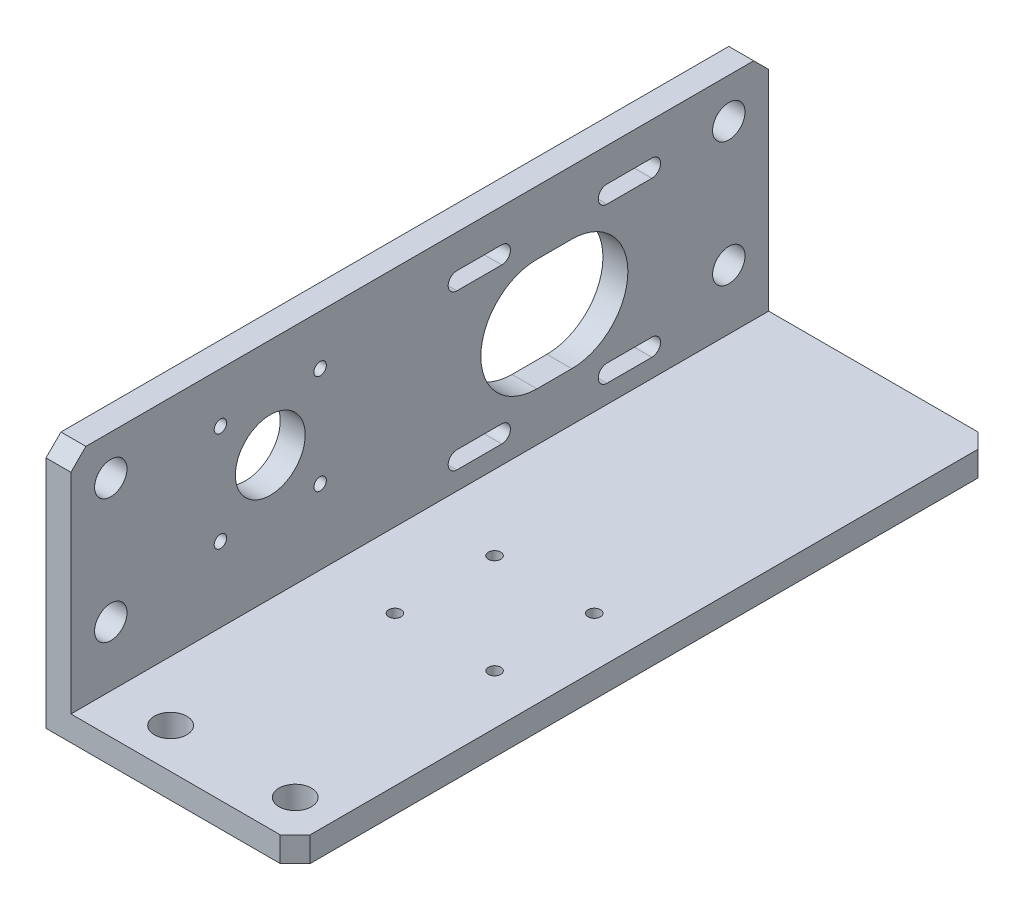
SolidWorks part; units mm, degrees
material "Lega 1060"
ref_plane "Piano frontale" through (0, 0, 0) normal (0, 0, 1) x (1, 0, 0)
ref_plane "Piano superiore" through (0, 0, 0) normal (0, 1, 0) x (1, 0, 0)
ref_plane "Piano destro" through (0, 0, 0) normal (1, 0, 0) x (0, 0, -1)
sketch "Schizzo1" plane through (0, 0, 0) normal (0, 0, 1) x (1, 0, 0)
  line L0 (0, 0) -> (0, 50)
  line L1 (0, 50) -> (5, 50)
  line L2 (5, 50) -> (5, 5)
  line L3 (5, 5) -> (50, 5)
  line L4 (50, 5) -> (50, 0)
  line L5 (50, 0) -> (0, 0)
  dimension "D1" = 5
  dimension "D2" = 5
  dimension "D3" = 50
  dimension "D4" = 50
extrude "Estrusione-Estrusione1" add sketch "Schizzo1" along normal blind 140
sketch "Schizzo2" plane through (0, 0, 0) normal (0, -1, 0) x (1, 0, 0)
  line L0 (5.4524, 132) -> (42.7933, 132) construction
  line L1 (0, 140) -> (50, 140) construction
  line L5 (50, 140) -> (50, 0) construction
  point P4 (17, 132)
  point P5 (42, 132)
  dimension "D1" = 8
  dimension "D2" = 25
  dimension "D3" = 8
sketch "Schizzo3" plane through (0, 0, 0) normal (-1, 0, 0) x (0, 0, 1)
  line L0 (132, 44.621) -> (132, 5.772) construction
  line L1 (140, 50) -> (140, 0) construction
  line L2 (140, 50) -> (0, 50) construction
  point P4 (132, 42)
  point P5 (132, 17)
  dimension "D1" = 8
  dimension "D2" = 8
  dimension "D3" = 25
hole_wizard "Foro Ø6.5 (6.5)-1" positions "Schizzo5" profile "Schizzo4" hole size "Ø6.5" standard "ISO" end condition through all
sketch "Schizzo5" plane through (0, 0, 0) normal (0, -1, 0) x (-1, 0, 0)
  point P0 (-17, -132)
  point P3 (-42, -132)
sketch "Schizzo4" plane through (17, 0, 132) normal (1, 0, 0) x (0, 0, -1)
  line L0 (0, 0) -> (0, 50)
  line L1 (0, 50) -> (3.25, 50)
  line L2 (3.25, 50) -> (3.25, 0)
  line L5 (3.25, 0) -> (0, 0)
  line L11 (0, -6.35) -> (0, 107.95) construction
  dimension "Thru Hole Dia." = 6.5
  dimension "Thru Hole Depth" = 50
hole_wizard "Foro Ø6.5 (6.5)-2" positions "Schizzo7" profile "Schizzo6" hole size "Ø6.5" standard "ISO"
sketch "Schizzo7" plane through (0, 0, 0) normal (-1, 0, 0) x (0, 0, 1)
  point P1 (132, 42)
  point P4 (132, 17)
sketch "Schizzo6" plane through (0, 42, 132) normal (0, 1, 0) x (0, 0, 1)
  line L0 (0, 0) -> (0, 6.9528)
  line L1 (0, 6.9528) -> (3.25, 5)
  line L2 (3.25, 5) -> (3.25, 0)
  line L5 (3.25, 0) -> (0, 0)
  line L10 (0, 6.9528) -> (-3.25, 5) construction
  line L11 (0, -6.35) -> (0, 107.95) construction
  dimension "Hole Dia." = 6.5
  dimension "Hole Depth" = 5
  dimension "Drill Angle" = 118
ref_plane "Piano1" through (0, 0, 70) normal (0, 0, 1) x (1, 0, 0)
mirror "Specchia1" about plane through (0, 0, 70) normal (0, 0, 1) of "Foro Ø6.5 (6.5)-2"
sketch "Schizzo8" plane through (0, 0, 0) normal (0, -1, 0) x (1, 0, 0)
  line L0 (30, 80) -> (7.0316, 80) construction
  line L1 (30, 80) -> (-7.1051, 42.8949) construction
  line L2 (0, 140) -> (50, 140) construction
  line L3 (50, 140) -> (50, 0) construction
  circle A0 centre (20, 70) radius 1.75
  circle A1 centre (20, 90) radius 1.75
  circle A2 centre (40, 90) radius 1.75
  circle A3 centre (40, 70) radius 1.75
  point P18 (30, 80)
  dimension "D3" = 3.5
  dimension "D1" = 60
  dimension "D2" = 20
  dimension "D4" = 45
  dimension "D5" = 20
  dimension "D6" = 4
sketch "Schizzo9" plane through (0, 0, 0) normal (-1, 0, 0) x (0, 0, 1)
  line L2 (140, 50) -> (0, 50) construction
  line L3 (140, 50) -> (140, 0) construction
  circle A4 centre (100, 30) radius 7
  point P18 (100, 30)
  dimension "D7" = 14
  dimension "D1" = 20
  dimension "D2" = 40
extrude "Taglio-Estrusione2" cut sketch "Schizzo9" against normal up to next
sketch "Schizzo11" plane through (0, 0, 0) normal (-1, 0, 0) x (0, 0, 1)
  line L0 (32.6037, 26) -> (56.4009, 26) construction
  line L1 (62.5563, 10.4437) -> (53.5563, 10.4437) construction
  line L2 (140, 0) -> (0, 0) construction
  line L3 (62.5563, 41.5563) -> (53.5563, 41.5563) construction
  line L4 (62.5563, 39.8063) -> (53.5563, 39.8063)
  line L5 (62.5563, 43.3063) -> (53.5563, 43.3063)
  line L6 (43, 26) -> (43, 48.418) construction
  line L7 (62.5563, 12.1937) -> (53.5563, 12.1937)
  line L8 (62.5563, 8.6937) -> (53.5563, 8.6937)
  line L9 (23.4437, 10.4437) -> (32.4437, 10.4437) construction
  line L10 (23.4437, 12.1937) -> (32.4437, 12.1937)
  line L11 (23.4437, 8.6937) -> (32.4437, 8.6937)
  line L12 (23.4437, 41.5563) -> (32.4437, 41.5563) construction
  line L13 (23.4437, 39.8063) -> (32.4437, 39.8063)
  line L14 (23.4437, 43.3063) -> (32.4437, 43.3063)
  line L15 (46.5, 26) -> (39.5, 26) construction
  line L16 (46.5, 14.75) -> (39.5, 14.75)
  line L17 (46.5, 37.25) -> (39.5, 37.25)
  arc A1 (62.5563, 39.8063) -> (62.5563, 43.3063) centre (62.5563, 41.5563) ccw
  arc A2 (62.5563, 12.1937) -> (62.5563, 8.6937) centre (62.5563, 10.4437) cw
  arc A3 (53.5563, 8.6937) -> (53.5563, 12.1937) centre (53.5563, 10.4437) cw
  arc A4 (23.4437, 12.1937) -> (23.4437, 8.6937) centre (23.4437, 10.4437) ccw
  arc A5 (32.4437, 8.6937) -> (32.4437, 12.1937) centre (32.4437, 10.4437) ccw
  arc A7 (53.5563, 43.3063) -> (53.5563, 39.8063) centre (53.5563, 41.5563) ccw
  arc A8 (23.4437, 39.8063) -> (23.4437, 43.3063) centre (23.4437, 41.5563) cw
  arc A9 (32.4437, 43.3063) -> (32.4437, 39.8063) centre (32.4437, 41.5563) cw
  arc A10 (46.5, 14.75) -> (46.5, 37.25) centre (46.5, 26) ccw
  arc A11 (39.5, 37.25) -> (39.5, 14.75) centre (39.5, 26) ccw
  point P10 (58.0563, 10.4437)
  point P13 (58.0563, 41.5563)
  point P18 (27.9437, 10.4437)
  point P20 (43, 26)
  point P33 (27.9437, 41.5563)
  point P40 (43, 26)
  dimension "D5" = 7
  dimension "D1" = 22.5
  dimension "D4" = 26
  dimension "D8" = 3.5
  dimension "D9" = 9
extrude "Taglio-Estrusione4" cut sketch "Schizzo11" against normal up to next
chamfer "Smusso1" distance 3 angle 45 4 edges at (50, 2.5, 0) (2.5, 50, 0) (2.5, 50, 140) (50, 2.5, 140)
sketch "Sketch4" plane through (0, 0, 0) normal (-1, 0, 0) x (0, 0, 1)
  line L0 (100, 30) -> (100, 45.3374) construction
  line L1 (100, 30) -> (85.4455, 44.5545) construction
  line L2 (100, 30) -> (85.4455, 30) construction
  point P3 (90, 40)
  point P5 (110, 40)
  point P6 (90, 20)
  point P8 (110, 20)
  dimension "D1" = 45
  dimension "D2" = 10
hole_wizard "M3 Tapped Hole1" positions "3DSketch3" profile "Sketch5" tap size "M3" standard "ISO" end condition through all
sketch3d "3DSketch3"
  point P0 (0, 40, 90)
  point P3 (0, 40, 110)
  point P6 (0, 20, 110)
  point P9 (0, 20, 90)
sketch "Sketch5" plane through (0, 40, 90) normal (0, 1, 0) x (0, 0, 1)
  line L0 (0, 0) -> (0, 50)
  line L1 (0, 50) -> (1.25, 50)
  line L2 (1.25, 50) -> (1.25, 0)
  line L5 (1.25, 0) -> (0, 0)
  line L11 (0, -6.35) -> (0, 107.95) construction
  dimension "Thru Tap Drill Dia." = 2.5
  dimension "Thru Tap Drill Depth" = 50
cosmetic thread "Cosmetic Thread1" parameters "D2"=3
cosmetic thread "Cosmetic Thread2" parameters "D2"=3
cosmetic thread "Cosmetic Thread3" parameters "D2"=3
cosmetic thread "Cosmetic Thread4" parameters "D2"=3
hole_wizard "M3 Tapped Hole2" positions "3DSketch4" profile "Sketch6" tap size "M3" standard "ISO" end condition through all
sketch3d "3DSketch4"
  point P0 (20, 0, 90)
  point P3 (40, 0, 90)
  point P6 (40, 0, 70)
  point P9 (20, 0, 70)
sketch "Sketch6" plane through (20, 0, 90) normal (1, 0, 0) x (0, 0, -1)
  line L0 (0, 0) -> (0, 50)
  line L1 (0, 50) -> (1.25, 50)
  line L2 (1.25, 50) -> (1.25, 0)
  line L5 (1.25, 0) -> (0, 0)
  line L11 (0, -6.35) -> (0, 107.95) construction
  dimension "Thru Tap Drill Dia." = 2.5
  dimension "Thru Tap Drill Depth" = 50
cosmetic thread "Cosmetic Thread5" parameters "D2"=3
cosmetic thread "Cosmetic Thread6" parameters "D2"=3
cosmetic thread "Cosmetic Thread7" parameters "D2"=3
cosmetic thread "Cosmetic Thread8" parameters "D2"=3
